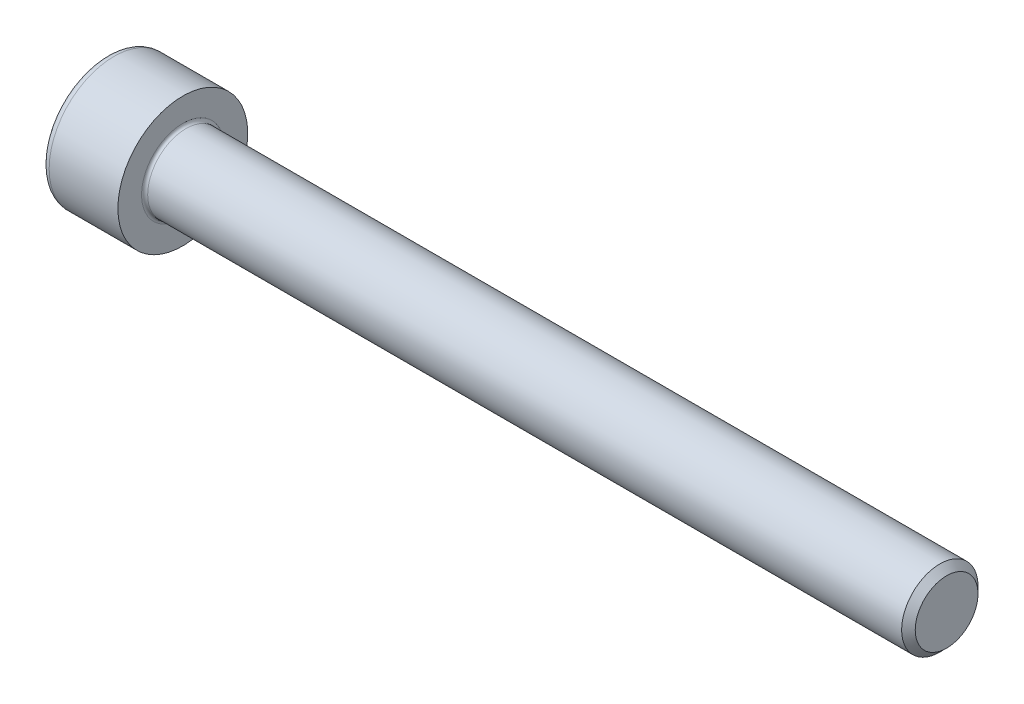
SolidWorks part; units mm, degrees
revolve "Base-Revolve" add sketch "BodySke"
sketch "BodySke" plane through (0, 0, 0) normal (0, 0, 1) x (1, 0, 0)
  line L0 (0, 0) -> (0, 4.25)
  line L1 (0, 4.25) -> (5, 4.25)
  line L2 (5, 4.25) -> (5, 2.5)
  line L3 (5, 2.5) -> (54.555, 2.5)
  line L4 (55, 2.055) -> (55, 0)
  line L5 (55, 0) -> (0, 0)
  line L6 (-31.75, 0) -> (127, 0) construction
  line L8 (55, 2.055) -> (54.555, 2.5)
  line L10 (55, -2.055) -> (54.555, -2.5) construction
  line L11 (5.8, 9.525) -> (5.8, 3.175) construction
  line L12 (33, 9.525) -> (33, 3.175) construction
  line L13 (-5, 9.525) -> (-5, 3.175) construction
  dimension "Diameter" = 5
  dimension "Head_dia" = 8.5
cosmetic thread "ThreadCosmetic"
fillet "Fillet1" radius 0.2 1 edges at (5, 0, 2.5)
fillet "Fillet2" radius 0.5 1 edges at (0, 0, 4.25)
ref_plane "Plane1" through (0, 0, 0) normal (0, 0, 1) x (1, 0, 0)
ref_plane "Plane2" through (0, 0, 0) normal (0, 1, 0) x (1, 0, 0)
ref_plane "Plane3" through (0, 0, 0) normal (1, 0, 0) x (0, 0, -1)
sketch "Sketch2" plane through (0, 0, 0) normal (0, 0, 1) x (1, 0, 0)
  line L0 (0, 2.01) -> (2.5, 2.01)
  line L1 (2.5, 2.01) -> (3.6605, 0)
  line L2 (-31.75, 0) -> (127, 0) construction
  line L3 (3.6605, 0) -> (0, 0)
  line L4 (0, 0) -> (0, 2.01)
  line L6 (0, 0) -> (47.625, 0) construction
  dimension "D1" = 2.01
  dimension "D2" = 60
revolve "Hex-PreBroach" cut sketch "Sketch2" angle 360 about L6
sketch "Sketch3" plane through (0, 0, 0) normal (-1, 0, 0) x (0, 0.5, 0.866)
  line L0 (1.1605, 2.01) -> (-1.1605, 2.01)
  line L1 (-1.1605, 2.01) -> (-2.3209, 0)
  line L2 (1.1605, 2.01) -> (2.3209, 0)
  line L3 (1.1605, -2.01) -> (2.3209, 0)
  line L4 (1.1605, -2.01) -> (-1.1605, -2.01)
  line L5 (-1.1605, -2.01) -> (-2.3209, 0)
  dimension "D1" = 2.01
  dimension "D2" = 2.01
extrude "Hex" cut sketch "Sketch3" against normal blind 2.5
sketch "ThdSchSke" plane through (0, 0, 0) normal (0, 0, 1) x (1, 0, 0)
  line L0 (33, -2.055) -> (32.6884, -2.5)
  line L1 (33, -2.055) -> (33.3116, -2.5)
  line L2 (33.3116, -2.5) -> (33.3116, -3.125)
  line L3 (-3.175, 0) -> (5.1513, 0) construction
  line L4 (0, 3.75) -> (0, -3.75) construction
  line L5 (33.3116, -3.125) -> (32.6884, -3.125)
  line L6 (32.6884, -3.125) -> (32.6884, -2.5)
  dimension "Diameter" = 5
  dimension "Thread_minor" = 4.11
revolve "ThreadSchematic" [suppressed] cut sketch "ThdSchSke" angle 360 about L3
pattern_linear "ThdSchPat" [suppressed]
equation "\"D2@Sketch3\" = \"Hex_size@Sketch3\" / 2"
equation "\"D1@Sketch3\" = \"Hex_size@Sketch3\" / 2"
equation "\"D1@Sketch2\" = \"Hex_size@Sketch3\" / 2"
equation "\"Thread_minor@ThreadCosmetic\"  =  \"Minor_dia@BodySke\""
equation "\"Depth@Sketch2\" =  \"Key_eng@Hex\""
equation "\"Thread_length@ThreadCosmetic\" = ((sgn( (\"Length@BodySke\" - \"Advance@BodySke\" * 3.0) - \"Thread_nom@BodySke\" )-1)*( (\"Length@BodySke\" - \"Advance@BodySke\" * 3.0) - \"Thread_nom@BodySke\" ))/-2+ \"Thread_nom@BodySke\""
equation "\"Thread_minor@ThdSchSke\" = \"Minor_dia@BodySke\""
equation "\"Diameter@ThdSchSke\" = \"Diameter@BodySke\""
equation "\"Overcut@ThdSchSke\" = \"Diameter@BodySke\" * 1.25"
equation "\"Start@ThdSchSke\" = \"Head_ht@BodySke\" + \"Length@BodySke\" - \"Thread_length@ThreadCosmetic\"  '---Non-countersunk---"
equation "\"Num_threads@ThdSchPat\" = int( \"Thread_length@ThreadCosmetic\" / \"Advance@BodySke\" + 0.999 )  + 1"
equation "\"Advance@ThdSchPat\" = \"Thread_length@ThreadCosmetic\" /  (\"Num_threads@ThdSchPat\" - 1) 'relax it"
equation "\"Num_threads@ThdSchPat\" = \"Num_threads@ThdSchPat\" - sgn( \"Num_threads@ThdSchPat\" - 1) '---chamfered tips only---"
